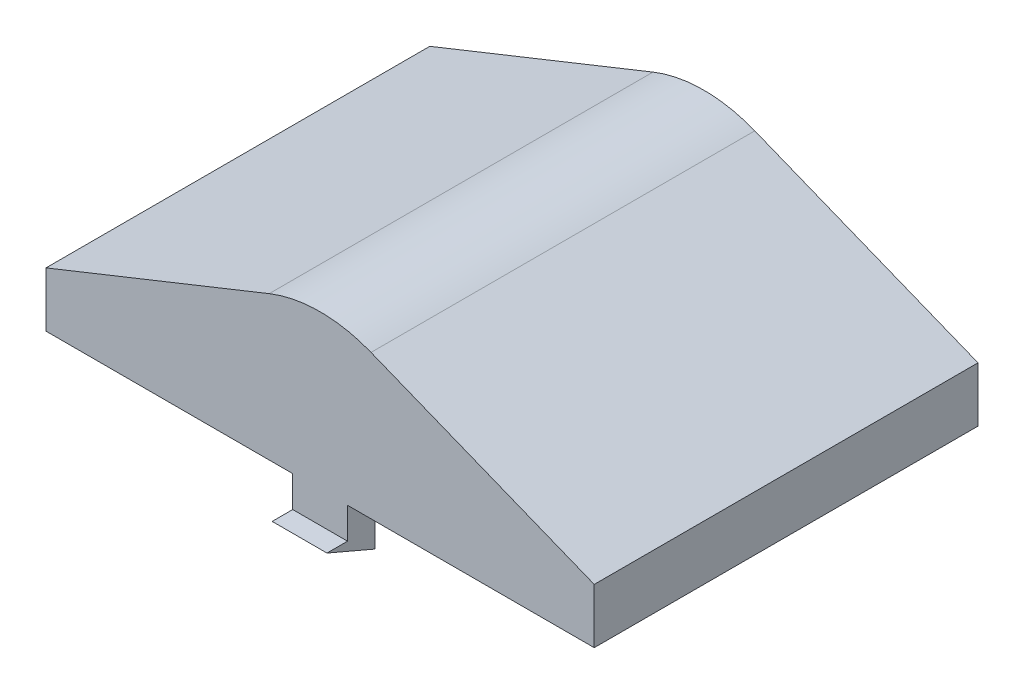
SolidWorks part; units mm, degrees
ref_plane "Front Plane" through (0, 0, 0) normal (0, 0, 1) x (1, 0, 0)
ref_plane "Top Plane" through (0, 0, 0) normal (0, 1, 0) x (1, 0, 0)
ref_plane "Right Plane" through (0, 0, 0) normal (1, 0, 0) x (0, 0, -1)
sketch "Sketch1" plane through (0, 0, 0) normal (0, 0, 1) x (1, 0, 0)
  line L0 (-10, 0) -> (10, 0)
  line L1 (10, 0) -> (10, 2)
  line L2 (10, 2) -> (0, 6)
  line L3 (0, 6) -> (0, 0) construction
  line L4 (-10, 2) -> (0, 6)
  line L5 (-10, 0) -> (-10, 2)
  dimension "D1" = 10
  dimension "D2" = 6
  dimension "D3" = 2
extrude "Extrude1" add sketch "Sketch1" along normal mid plane 14
fillet "Fillet1" radius 5 1 edges at (0, 6, 0)
shell "Shell1" thickness 1 removed face at (0, 0, 0)
sketch "Sketch2" plane through (0, 0, 0) normal (1, 0, 0) x (0, 0, -1)
  line L0 (-7, 0) -> (-7, 2) construction
  line L1 (-6, 0) -> (-7, 0)
  line L2 (-6, 0) -> (-6, -1.8852)
  line L3 (7, 5.6148) -> (-7, 5.6148) construction
  line L4 (-7, 0) -> (-7, -1.1352)
  line L5 (-6, -1.8852) -> (-7.75, -1.1352)
  line L6 (-7.75, -1.1352) -> (-7, -1.1352)
  dimension "D1" = 7.5
  dimension "D2" = 6.75
  dimension "D3" = 1.75
extrude "Extrude2" add sketch "Sketch2" along normal mid plane 2
mirror "Mirror1" about plane through (0, 0, 0) normal (0, 0, 1) of "Extrude2"
